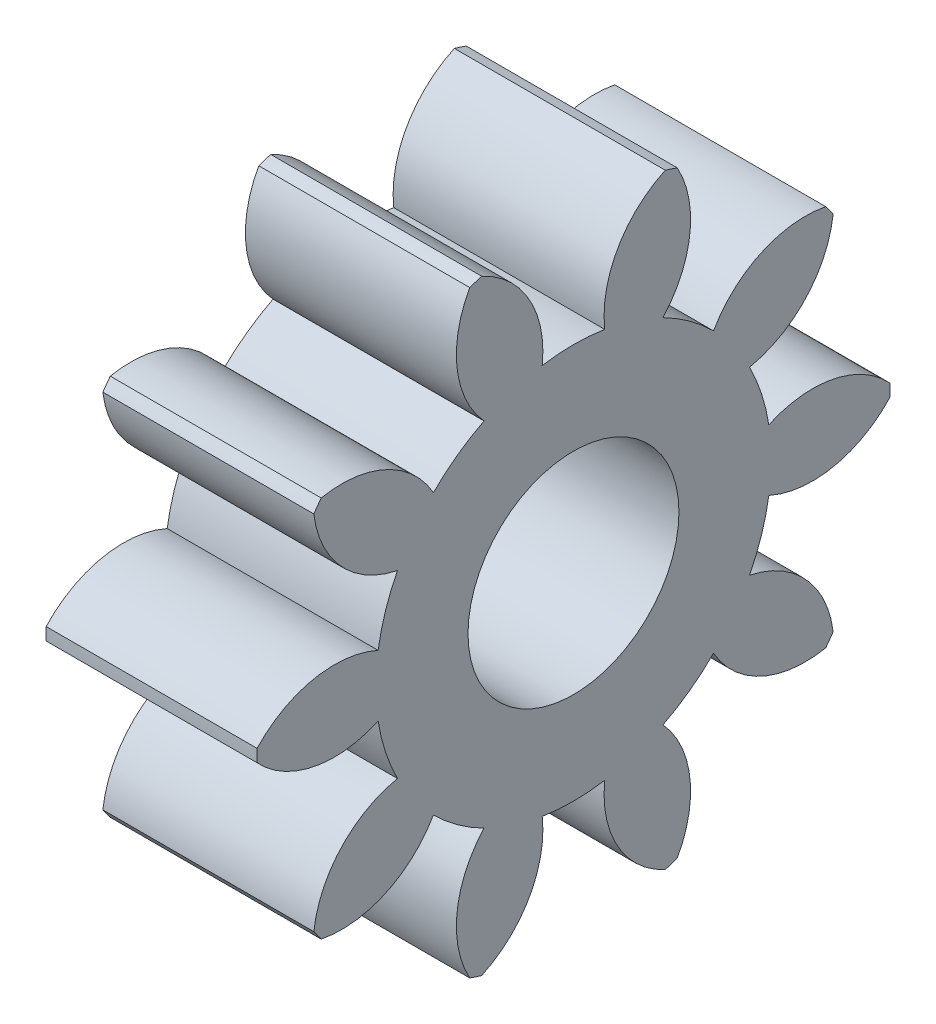
SolidWorks part; units mm, degrees
ref_plane "Plane1" through (0, 0, 0) normal (0, 0, 1) x (1, 0, 0)
ref_plane "Plane2" through (0, 0, 0) normal (0, 1, 0) x (1, 0, 0)
ref_plane "Plane3" through (0, 0, 0) normal (1, 0, 0) x (0, 0, -1)
other "Configuration Table"
sketch "HoldingSke" plane through (0, 0, 0) normal (0, 1, 0) x (1, 0, 0)
  line L0 (0, 0) -> (0.9848, -0.1736)
  line L1 (-15, 0) -> (100, 0) construction
  line L2 (0, 0) -> (-2.1039, 2.3779)
  line L3 (0, 0) -> (-11.863, 4.5341)
  line L4 (0, 0) -> (8.5048, 1.4996)
  line L5 (0, 0) -> (-46.8476, -17.4728)
  line L6 (0, 0) -> (-3.3159, -2.2372)
  line L7 (-2.1039, 2.3779) -> (8.6586, 51.2059)
  line L8 (-76.2, 54.61) -> (-75.5, 54.61)
  line L9 (-71.009, 38.7566) -> (-53.1078, 45.2721)
  line L10 (-76.2, 71.12) -> (104.1128, 71.12)
  line L11 (0, 0) -> (-4, 0)
  line L12 (-76.2, 101.6) -> (-76.162, 101.6)
  line L13 (24.9733, 27.94) -> (52.9518, 28.4284)
  line L14 (24.9733, 27.94) -> (24.9743, 27.94)
  line L15 (24.9733, 27.94) -> (100.4006, 29.5858)
  line L16 (-63.627, -1) -> (-12.827, -1)
  circle A0 centre (0, 0) radius 2
  circle A1 centre (0, 0) radius 3.749
  circle A2 centre (0, 0) radius 37.5
  circle A3 centre (0, 0) radius 2
  dimension "Num_teeth" = 10
  dimension "Pitch_radius" = 180.3128
  dimension "Width" = 4
  dimension "Thickness" = 4
sketch "BasProSke" plane through (0, 0, 0) normal (0, 1, 0) x (1, 0, 0)
  line L0 (-10, 0) -> (60, 0) construction
  line L1 (0, 0) -> (0, 6)
  line L2 (0, 0) -> (4, 0)
  line L3 (4, 0) -> (4, 6)
  line L4 (4, 6) -> (0, 6)
  dimension "Thickness" = 4
  dimension "Diameter" = 12
revolve "Base-Revolve" add sketch "BasProSke" angle 360 about L0
sketch "TooCutSke" plane through (0, 0, 0) normal (1, 0, 0) x (0, 0, -1)
  line L1 (0, 0) -> (0, 107) construction
  line L2 (0, 0) -> (-0.8485, 4.9275) construction
  line L3 (0, 0) -> (-3.0584, 9.4126) construction
  line L4 (-0.8485, 4.9275) -> (-1.5292, 4.7063) construction
  arc A0 (0.5928, 3.7018) -> (-0.5928, 3.7018) centre (0, 0) ccw
  arc A1 (1.7758, 5.7578) -> (-1.7758, 5.7578) centre (0, 0) ccw
  circle A2 centre (0, 0) radius 5 construction
  circle A3 centre (0, 0) radius 4.6985 construction
  arc A4 (-0.5928, 3.7018) -> (-1.7758, 5.7578) centre (-2.5801, 3.9267) ccw
  arc A5 (1.7758, 5.7578) -> (0.5928, 3.7018) centre (2.5801, 3.9267) ccw
extrude "ToothCut" cut sketch "TooCutSke" along normal through all
fillet "Breaks" [suppressed] radius 0.02 tangent propagation no
fillet "RootFillets" [suppressed] radius 0.251
pattern_circular "TeethCuts" count 10 every 36 about axis through (-10, 0, 0) along (1, 0, 0) of "ToothCut", "RootFillets", "Breaks"
sketch "HubNeaOneSke" plane through (0, 0, 0) normal (-1, 0, 0) x (0, 0, 1)
  circle A0 centre (0, 0) radius 3.749
  dimension "Diameter" = 7.498
extrude "HubNearOne" [suppressed] add sketch "HubNeaOneSke" along normal blind 46.0001
sketch "HubNeaBotSke" plane through (0, 0, 0) normal (-1, 0, 0) x (0, 0, 1)
  circle A0 centre (0, 0) radius 3.749
  dimension "Diameter" = 7.498
extrude "HubNearBoth" [suppressed] add sketch "HubNeaBotSke" along normal blind 23
ref_plane "FarPln" through (4, 0, 0) normal (1, 0, 0) x (0, 0, -1)
sketch "HubFarSke" plane through (4, 0, 0) normal (1, 0, 0) x (0, 0, -1)
  circle A0 centre (0, 0) radius 3.749
  dimension "Diameter" = 7.498
extrude "HubFar" [suppressed] add sketch "HubFarSke" along normal blind 23
sketch "BorSke" plane through (0, 0, 0) normal (1, 0, 0) x (0, 0, -1)
  circle A0 centre (0, 0) radius 2
  dimension "Diameter" = 4
extrude "Bore" cut sketch "BorSke" along normal mid plane 100.0001
sketch "KeySke" plane through (0, 0, 0) normal (1, 0, 0) x (0, 0, -1)
  line L0 (-0.8, 0) -> (-0.8, 2.7)
  line L1 (-0.8, 2.7) -> (0.8, 2.7)
  line L2 (0.8, 2.7) -> (0.8, 0)
  line L3 (0, 0) -> (0, 34) construction
  line L4 (-0.8, 0) -> (0.8, 0)
  dimension "Width" = 1.6
extrude "Keyway" [suppressed] cut sketch "KeySke" along normal mid plane 100.0001
pattern_circular "Keyway2" [suppressed] count 2 every 90 about axis through (-10, 0, 0) along (1, 0, 0)
equation "' \"Module@HoldingSke\" = 6.35"
equation "' \"Num_teeth@HoldingSke\" = 12"
equation "' \"Ap@HoldingSke\" =  20"
equation "' \"Ap@HoldingSke\" = 20"
equation "' \"Width@HoldingSke\" = 0.5 * 25.4"
equation "' \"Hub_dia@HoldingSke\"= 1 * 25.4"
equation "' \"Hub_dia@HoldingSke\" = 1 * 25.4"
equation "' \"Overall_len@HoldingSke\" = 1.0 * 25.4"
equation "' \"Bore@HoldingSke\" = 0.75 * 25.4"
equation "' \"T_dim@HoldingSke\" = 0.1 * 25.4"
equation "' \"Width@KeySke\" = 0.25 * 25.4"
equation "' \"Show_teeth@HoldingSke\" = 13"
equation "' \"Backlash@HoldingSke\" = 0.009 * 25.4"
equation "' \"Addendum_fac@HoldingSke\" = 1.0"
equation "' \"Dedendum_fac@HoldingSke\" = 1.25"
equation "' \"Dedendum_add@HoldingSke\" = 0.00005 * 25.4"
equation "' \"Clearance_fac@HoldingSke\" = 0.25"
equation "\"Pitch@HoldingSke\" = 1 / \"Module@HoldingSke\""
equation "\"Overcut_dia@TooCutSke\" = (\"Num_teeth@HoldingSke\" + 2 * \"Addendum_fac@HoldingSke\") / \"Pitch@HoldingSke\" + 0.002 * 25.4"
equation "\"Pitch_dia@TooCutSke\" = \"Num_teeth@HoldingSke\" / \"Pitch@HoldingSke\""
equation "\"Base_dia@TooCutSke\" = \"Num_teeth@HoldingSke\" / \"Pitch@HoldingSke\" * cos((\"Ap@HoldingSke\"  * 3.14159265 / 180))"
equation "\"Root_dia@TooCutSke\" = (\"Num_teeth@HoldingSke\" + 2) / \"Pitch@HoldingSke\" - 2 * (\"Addendum_fac@HoldingSke\" + \"Dedendum_fac@HoldingSke\") / \"Pitch@HoldingSke\" - \"Dedendum_add@HoldingSke\" * 2"
equation "\"Half_ang@TooCutSke\" = 180 / \"Num_teeth@HoldingSke\""
equation "\"Half_CT@TooCutSke\" = \"Num_teeth@HoldingSke\" / \"Pitch@HoldingSke\" * sin((3.14159265 / 2 / \"Num_teeth@HoldingSke\")) / 2 - 7 * \"Backlash@HoldingSke\" / 4"
equation "\"Flank_rad@TooCutSke\" = \"Num_teeth@HoldingSke\" / \"Pitch@HoldingSke\" / 5"
equation "\"Radius@RootFillets\" = \"Clearance_fac@HoldingSke\" / \"Pitch@HoldingSke\" + \"Dedendum_add@HoldingSke\""
equation "\"Break_rad@Breaks\" = 0.02 / \"Pitch@HoldingSke\""
equation "\"Thickness@HoldingSke\" = \"Width@HoldingSke\""
equation "\"OAL@HoldingSke\" = \"Thickness@HoldingSke\""
equation "\"MHD@HoldingSke\" = (\"Num_teeth@HoldingSke\" + 2) / \"Pitch@HoldingSke\" - 2 * (\"Addendum_fac@HoldingSke\" + \"Dedendum_fac@HoldingSke\")  / \"Pitch@HoldingSke\" - \"Dedendum_add@HoldingSke\" * 2"
equation "\"MBD@HoldingSke\" = (\"Num_teeth@HoldingSke\" + 2) / \"Pitch@HoldingSke\" - 2 * (\"Addendum_fac@HoldingSke\" + \"Dedendum_fac@HoldingSke\")  / \"Pitch@HoldingSke\" - \"Dedendum_add@HoldingSke\" * 2 - 0.002 * 25.4"
equation "\"MHD@HoldingSke\" = ((sgn( \"MHD@HoldingSke\" - \"Hub_dia@HoldingSke\" )-1)*( \"MHD@HoldingSke\" - \"Hub_dia@HoldingSke\" ))/-2+ \"Hub_dia@HoldingSke\""
equation "\"MBD@HoldingSke\" = ((sgn( \"MBD@HoldingSke\" - \"Bore@HoldingSke\" )-1)*( \"MBD@HoldingSke\" - \"Bore@HoldingSke\" ))/-2+ \"Bore@HoldingSke\""
equation "\"OAL@HoldingSke\" = ((sgn( \"OAL@HoldingSke\" - \"Overall_len@HoldingSke\" )+1)*( \"OAL@HoldingSke\" - \"Overall_len@HoldingSke\" ))/2 + \"Overall_len@HoldingSke\" + 0.000002 * 25.4"
equation "\"Num_teeth@TeethCuts\" = int( \"Show_teeth@HoldingSke\" ) + 1"
equation "\"Num_teeth@TeethCuts\" = ((sgn( \"Num_teeth@TeethCuts\" - \"Num_teeth@HoldingSke\" )-1)*( \"Num_teeth@TeethCuts\" - \"Num_teeth@HoldingSke\" ))/-2+ \"Num_teeth@HoldingSke\""
equation "\"Num_teeth@TeethCuts\" = ((sgn( \"Num_teeth@TeethCuts\" - 2.0)+1)*( \"Num_teeth@TeethCuts\" - 2.0))/2 +2.0"
equation "\"Angle@TeethCuts\" = 360.0 / \"Num_teeth@HoldingSke\""
equation "\"Diameter@BasProSke\" = (\"Num_teeth@HoldingSke\" + 2 * \"Addendum_fac@HoldingSke\") / \"Pitch@HoldingSke\""
equation "\"Thickness@BasProSke\"  = \"Thickness@HoldingSke\""
equation "' \"Fillet_rad@BasProSke\" =  \"Thickness@HoldingSke\" * 0.05"
equation "' \"Fillet_rad@BasProSke\" = \"Thickness@HoldingSke\" * 0.05"
equation "\"MHD@HoldingSke\" = ((sgn( \"MHD@HoldingSke\" - \"Root_dia@TooCutSke\" )-1)*( \"MHD@HoldingSke\" - \"Root_dia@TooCutSke\" ))/-2+ \"Root_dia@TooCutSke\""
equation "\"Diameter@HubNeaOneSke\" = \"MHD@HoldingSke\""
equation "\"Length@HubNearOne\" = \"OAL@HoldingSke\" - \"Thickness@BasProSke\""
equation "\"Diameter@HubNeaBotSke\" = \"MHD@HoldingSke\""
equation "\"Length@HubNearBoth\" = ( \"OAL@HoldingSke\" - \"Thickness@BasProSke\" ) / 2.0"
equation "\"Thickness@FarPln\" = \"Thickness@BasProSke\""
equation "\"Diameter@HubFarSke\" = \"MHD@HoldingSke\""
equation "\"Length@HubFar\" = ( \"OAL@HoldingSke\" - \"Thickness@BasProSke\" ) / 2.0"
equation "\"Diameter@BorSke\" = \"MBD@HoldingSke\""
equation "\"D1@Bore\" = \"OAL@HoldingSke\" * 2.0"
equation "\"D1@Keyway\" = \"OAL@HoldingSke\" * 2.0"
equation "\"Offset@KeySke\" = \"T_dim@HoldingSke\" + \"MBD@HoldingSke\" / 2.0"
